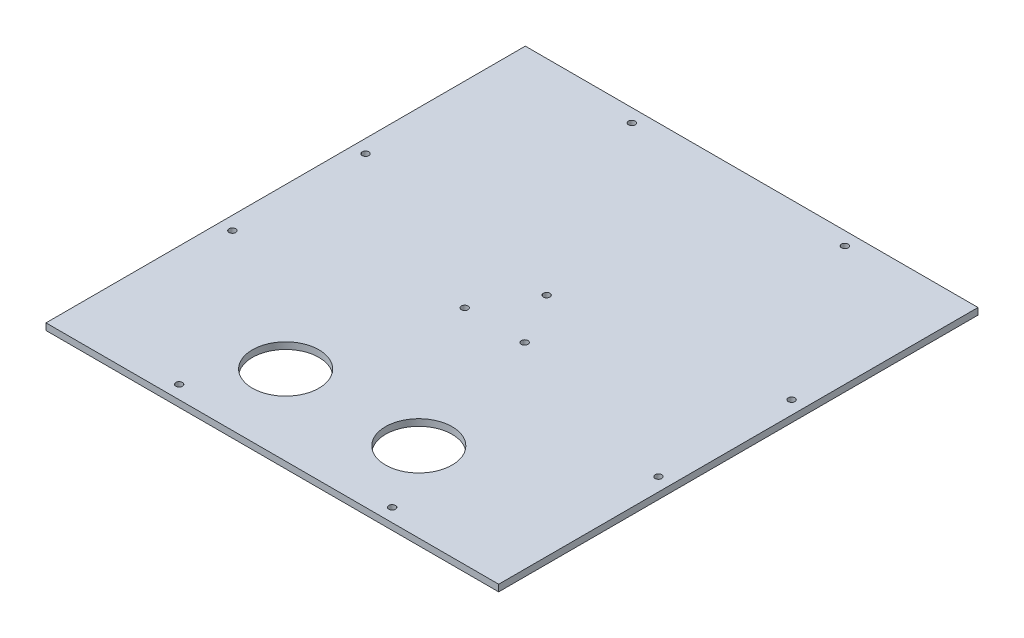
SolidWorks part; units mm, degrees
material "6061-T6 (SS)"
ref_plane "Front Plane" through (0, 0, 0) normal (0, 0, 1) x (1, 0, 0)
ref_plane "Top Plane" through (0, 0, 0) normal (0, 1, 0) x (1, 0, 0)
ref_plane "Right Plane" through (0, 0, 0) normal (1, 0, 0) x (0, 0, -1)
sketch "Sketch1" plane through (0, 0, 0) normal (0, 1, 0) x (1, 0, 0)
  line L1 (0, 0) -> (215.9, 0)
  line L2 (0, 0) -> (0, 228.6)
  line L3 (0, 228.6) -> (215.9, 228.6)
  line L4 (215.9, 0) -> (215.9, 228.6)
  dimension "D1" = 215.9
  dimension "D2" = 228.6
extrude "Boss-Extrude1" add sketch "Sketch1" along normal blind 3.175
sketch "Sketch2" plane through (0, 3.175, 0) normal (0, 1, 0) x (1, 0, 0)
  line L0 (139.7, 38.1) -> (76.2, 38.1) construction
  line L2 (139.7, 38.1) -> (215.9, 38.1) construction
  line L3 (215.9, 0) -> (215.9, 228.6) construction
  line L4 (76.2, 38.1) -> (0, 38.1) construction
  line L5 (0, 0) -> (215.9, 0) construction
  line L6 (0, 228.6) -> (0, 0) construction
  circle A0 centre (139.7, 38.1) radius 15.875
  circle A1 centre (76.2, 38.1) radius 15.875
  dimension "D1" = 31.75
  dimension "D2" = 38.1
  dimension "D3" = 63.5
extrude "Cut-Extrude1" cut sketch "Sketch2" against normal through all
sketch "Sketch3" plane through (0, 3.175, 0) normal (0, 1, 0) x (1, 0, 0)
  line L0 (0, 228.6) -> (0, 0) construction
  line L1 (0, 0) -> (215.9, 0) construction
  circle A0 centre (107.95, 130.81) radius 1.5875
  circle A1 centre (122.2481, 106.045) radius 1.5875
  circle A2 centre (93.6519, 106.045) radius 1.5875
  point P0 (0, 114.3)
  point P1 (107.95, 0)
  point P4 (107.95, 114.3)
  dimension "D2" = 3.175
  dimension "D1" = 16.51
  dimension "D3" = 3
extrude "Cut-Extrude2" cut sketch "Sketch3" against normal through all
sketch "Sketch4" plane through (0, 3.175, 0) normal (0, 1, 0) x (1, 0, 0)
  line L0 (215.9, 228.6) -> (0, 228.6) construction
  line L1 (0, 228.6) -> (0, 0) construction
  line L2 (0, 0) -> (215.9, 0) construction
  line L3 (107.95, 228.6) -> (107.95, 0) construction
  circle A0 centre (6.35, 146.05) radius 1.5875
  circle A1 centre (6.35, 82.55) radius 1.5875
  circle A2 centre (57.15, 6.35) radius 1.5875
  circle A3 centre (57.15, 222.25) radius 1.5875
  circle A4 centre (158.75, 6.35) radius 1.5875
  circle A5 centre (209.55, 82.55) radius 1.5875
  circle A6 centre (209.55, 146.05) radius 1.5875
  circle A7 centre (158.75, 222.25) radius 1.5875
  point P14 (107.95, 0)
  point P15 (107.95, 228.6)
  dimension "D1" = 3.175
  dimension "D2" = 6.35
  dimension "D3" = 6.35
  dimension "D4" = 6.35
  dimension "D5" = 6.35
  dimension "D6" = 57.15
  dimension "D7" = 57.15
  dimension "D8" = 82.55
  dimension "D9" = 82.55
extrude "Cut-Extrude3" cut sketch "Sketch4" against normal through all
